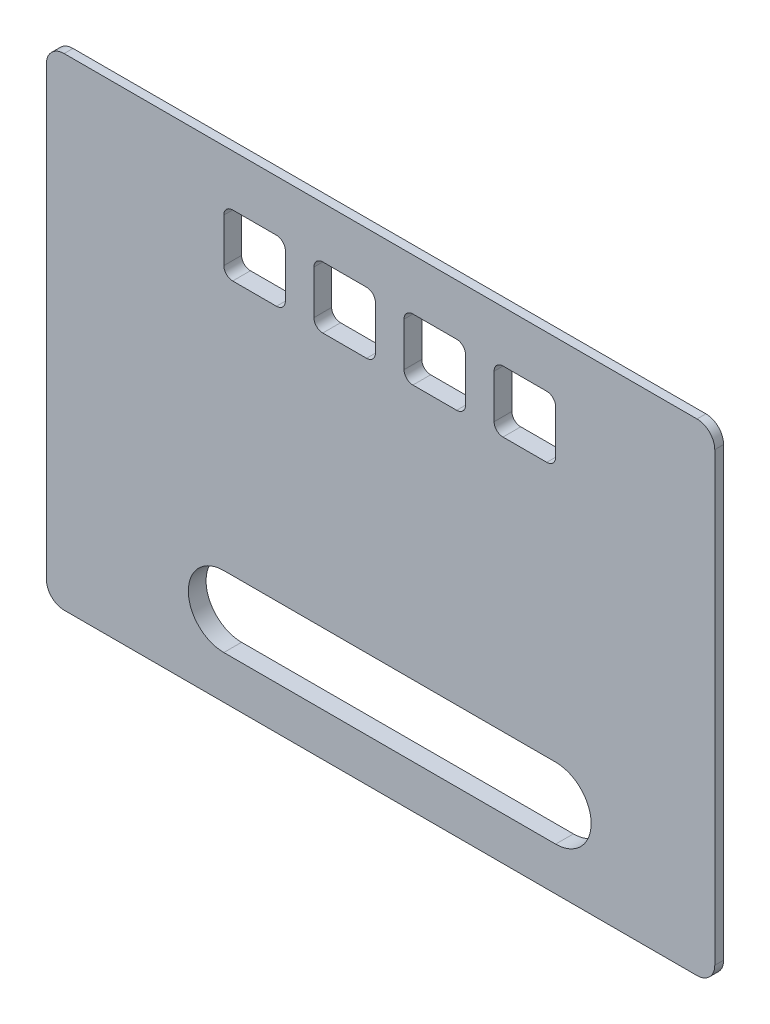
SolidWorks part; units mm, degrees
ref_plane "Спереди" through (0, 0, 0) normal (0, 0, 1) x (1, 0, 0)
ref_plane "Сверху" through (0, 0, 0) normal (0, 1, 0) x (1, 0, 0)
ref_plane "Справа" through (0, 0, 0) normal (1, 0, 0) x (0, 0, -1)
other "Configuration Table"
sketch "Эскиз1" plane through (0, 0, 0) normal (0, 0, 1) x (1, 0, 0)
  line L1 (0, 3) -> (107, 3)
  line L2 (0, 3) -> (0, 77)
  line L3 (0, 77) -> (107, 77)
  line L4 (107, 3) -> (107, 77)
extrude "Бобышка-Вытянуть1" add sketch "Эскиз1" along normal blind 3
sketch "Эскиз2" plane through (0, 0, 0) normal (0, 0, 1) x (1, 0, 0)
  line L1 (-3, 0) -> (110, 0)
  line L2 (-3, 0) -> (-3, 80)
  line L3 (-3, 80) -> (110, 80)
  line L4 (110, 0) -> (110, 80)
extrude "Бобышка-Вытянуть2" add sketch "Эскиз2" along normal blind 1.5 from offset 1.5
sketch "Эскиз3" plane through (0.75, 0, 3) normal (0, 0, 1) x (1, 0, 0)
  line L0 (26.25, 13.3) -> (82.35, 13.3) construction
  line L1 (26.25, 62.45) -> (36.65, 62.45)
  line L2 (26.25, 62.45) -> (26.25, 72.85)
  line L3 (26.25, 72.85) -> (36.65, 72.85)
  line L4 (36.65, 62.45) -> (36.65, 72.85)
  line L5 (41.483, 62.45) -> (51.883, 62.45)
  line L6 (41.483, 62.45) -> (41.483, 72.85)
  line L7 (41.483, 72.85) -> (51.883, 72.85)
  line L8 (51.883, 62.45) -> (51.883, 72.85)
  line L9 (56.717, 62.45) -> (67.117, 62.45)
  line L10 (56.717, 62.45) -> (56.717, 72.85)
  line L11 (56.717, 72.85) -> (67.117, 72.85)
  line L12 (67.117, 62.45) -> (67.117, 72.85)
  line L13 (71.95, 62.45) -> (82.35, 62.45)
  line L14 (71.95, 62.45) -> (71.95, 72.85)
  line L15 (71.95, 72.85) -> (82.35, 72.85)
  line L16 (82.35, 62.45) -> (82.35, 72.85)
  line L19 (26.25, 19.3) -> (82.35, 19.3)
  line L20 (26.25, 7.3) -> (82.35, 7.3)
  arc A2 (26.25, 19.3) -> (26.25, 7.3) centre (26.25, 13.3) ccw
  arc A3 (82.35, 7.3) -> (82.35, 19.3) centre (82.35, 13.3) ccw
  point P18 (54.3, 13.3)
extrude "Вырез-Вытянуть1" cut sketch "Эскиз3" against normal blind 5
sketch "Эскиз4" plane through (0, 0, 0) normal (0, 0, 1) x (1, 0, 0)
  line L1 (0, 77) -> (107, 77)
  line L2 (0, 77) -> (0, 78.5)
  line L3 (0, 78.5) -> (107, 78.5)
  line L4 (107, 77) -> (107, 78.5)
extrude "top_rear_inner_extension_1p5mm" add sketch "Эскиз4" along normal blind 3
sketch "Эскиз5" plane through (0, 0, 0) normal (0, 0, 1) x (1, 0, 0)
  line L1 (-3, 80) -> (110, 80)
  line L2 (-3, 80) -> (-3, 81.5)
  line L3 (-3, 81.5) -> (110, 81.5)
  line L4 (110, 80) -> (110, 81.5)
extrude "top_rear_outer_skin_extension_1p5mm" add sketch "Эскиз5" along normal blind 1.5 from offset 1.5
fillet "tool_D3_R1p5_button_corners" radius 1.5 16 edges at (72.7, 72.85, 1.5) (83.1, 72.85, 1.5) (83.1, 62.45, 1.5) (72.7, 62.45, 1.5) (57.467, 72.85, 1.5) (67.867, 72.85, 1.5) (67.867, 62.45, 1.5) (57.467, 62.45, 1.5) (42.233, 72.85, 1.5) (52.633, 72.85, 1.5) (52.633, 62.45, 1.5) (42.233, 62.45, 1.5) (27, 62.45, 1.5) (37.4, 62.45, 1.5) (37.4, 72.85, 1.5) (27, 72.85, 1.5) tangent propagation no
fillet "tool_D3_R3_top_outer_contour" radius 3 4 edges at (-3, 81.5, 2.25) (110, 81.5, 2.25) (110, 0, 2.25) (-3, 0, 2.25)
